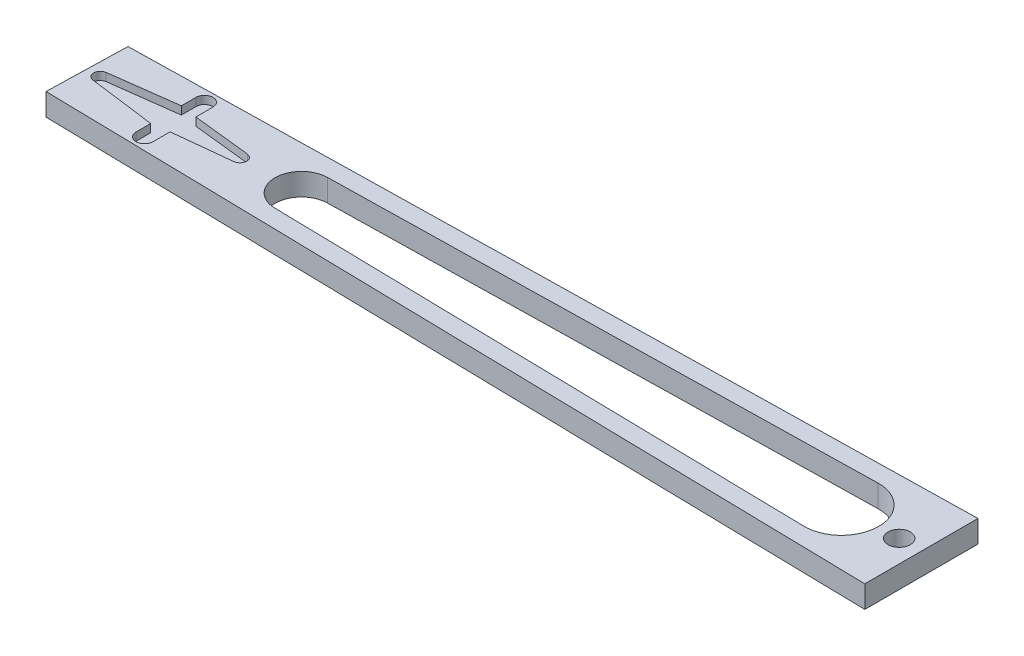
SolidWorks part; units mm, degrees
ref_plane "Front Plane" through (0, 0, 0) normal (0, 0, 1) x (1, 0, 0)
ref_plane "Top Plane" through (0, 0, 0) normal (0, 1, 0) x (1, 0, 0)
ref_plane "Right Plane" through (0, 0, 0) normal (1, 0, 0) x (0, 0, -1)
sketch "Sketch1" plane through (0, 0, 0) normal (0, 1, 0) x (1, 0, 0)
  line L9 (79.4808, -42.6859) -> (-42.0564, -45.0625)
  line L29 (-90.0051, -41.9994) -> (-90.48, -59.9931)
  line L30 (-90.48, -59.9931) -> (97.6447, -63.8155)
  line L31 (97.6447, -63.8155) -> (97.6447, -38.3299)
  line L32 (97.6447, -38.3299) -> (-90.0051, -41.9994)
  line L33 (-90.2426, -50.9963) -> (97.6447, -51.0727) construction
  line L34 (-70.5503, -44.2475) -> (-70.553, -51.0043) construction
  line L35 (-72.4503, -44.2475) -> (-72.4503, -47.5475)
  line L36 (-68.6503, -57.7475) -> (-68.6503, -53.8975)
  line L37 (-87.4449, -49.5102) -> (-72.4503, -47.5475)
  line L38 (-87.4449, -52.4848) -> (-72.4503, -54.4475)
  line L39 (-55.6448, -49.511) -> (-68.6503, -48.0975)
  line L40 (-55.6409, -52.5091) -> (-68.6503, -53.8975)
  line L41 (-68.6503, -48.0975) -> (-68.6503, -44.2475)
  line L42 (-72.4503, -54.4475) -> (-72.4503, -57.7475)
  line L43 (-52.8078, -41.272) -> (-52.8078, -60.7586)
  line L48 (-49.8078, -41.272) -> (-49.8078, -41.2133)
  line L51 (-49.8078, -41.272) -> (-49.8078, -60.7586) construction
  line L53 (-42.0612, -56.9692) -> (79.474, -59.4447)
  line L54 (93.6447, -42.4089) -> (-86.1073, -45.9239) construction
  line L56 (-86.3752, -56.0757) -> (93.6447, -59.7334) construction
  line L58 (-86.1073, -45.9239) -> (-86.3752, -56.0757) construction
  line L59 (93.6447, -59.7334) -> (93.6447, -42.4089) construction
  arc A10 (-87.4449, -49.5102) -> (-87.4449, -52.4848) centre (-87.2503, -50.9975) ccw
  arc A11 (-55.6409, -52.5091) -> (-55.6448, -49.511) centre (-55.8078, -51.0103) ccw
  arc A12 (-72.4503, -57.7475) -> (-68.6503, -57.7475) centre (-70.5503, -57.7475) ccw
  arc A13 (-68.6503, -44.2475) -> (-72.4503, -44.2475) centre (-70.5503, -44.2475) ccw
  circle A14 centre (-70.553, -51.0043) radius 1.275
  circle A15 centre (-70.553, -51.0043) radius 2.35
  circle A16 centre (92.6447, -51.0707) radius 2.5
  arc A17 (66.1628, -58.2338) -> (66.2469, -58.2343) centre (66.248, -51.0599) ccw
  arc A20 (66.2937, -43.8857) -> (66.208, -43.8857) centre (66.248, -51.0599) ccw
  arc A21 (-42.0564, -45.0625) -> (-42.0612, -56.9692) centre (-41.94, -51.0159) ccw
  arc A22 (79.474, -59.4447) -> (79.4808, -42.6859) centre (79.6447, -51.0654) ccw
  point P1 (-48.8078, -41.272)
  point P4 (-48.8078, -60.7586)
  point P42 (-54.2997, -51.0083)
  point P45 (-88.7503, -50.9975)
  point P65 (94.6498, -46.8901)
  point P66 (-87.0785, -45.8643)
  point P67 (-87.396, -57.8974)
  point P68 (94.6498, -60.8578)
  dimension "D8" = 5
  dimension "D9" = 5
  dimension "D1" = 188.1247
  dimension "D2" = 187.8872
  dimension "D3" = 4
  dimension "D4" = 9
  dimension "D5" = 18
  dimension "D6" = 3
  dimension "D7" = 3
extrude "Boss-Extrude1" add sketch "Sketch1" along normal blind 5 contours L43 L32 L29 L30 A13 L41 L39 A11 L40 L36 A12 L42 L38 A10 L37 L35 | L32 L43 L30 L31 A22 L53 A21 L9 A16 region at (-71.3982, 0, 42.0598) region at (-51.278, 0, 42.7683)
extrude "Boss-Extrude2" add sketch "Sketch1<16>" along normal blind 3.2 contours L39 L41 A13 L35 L37 A10 L38 L42 A12 L36 L40 A11
sketch "Sketch1<16>" plane through (0, 0, 0) normal (0, 1, 0) x (1, 0, 0) same geometry as "Sketch1"
